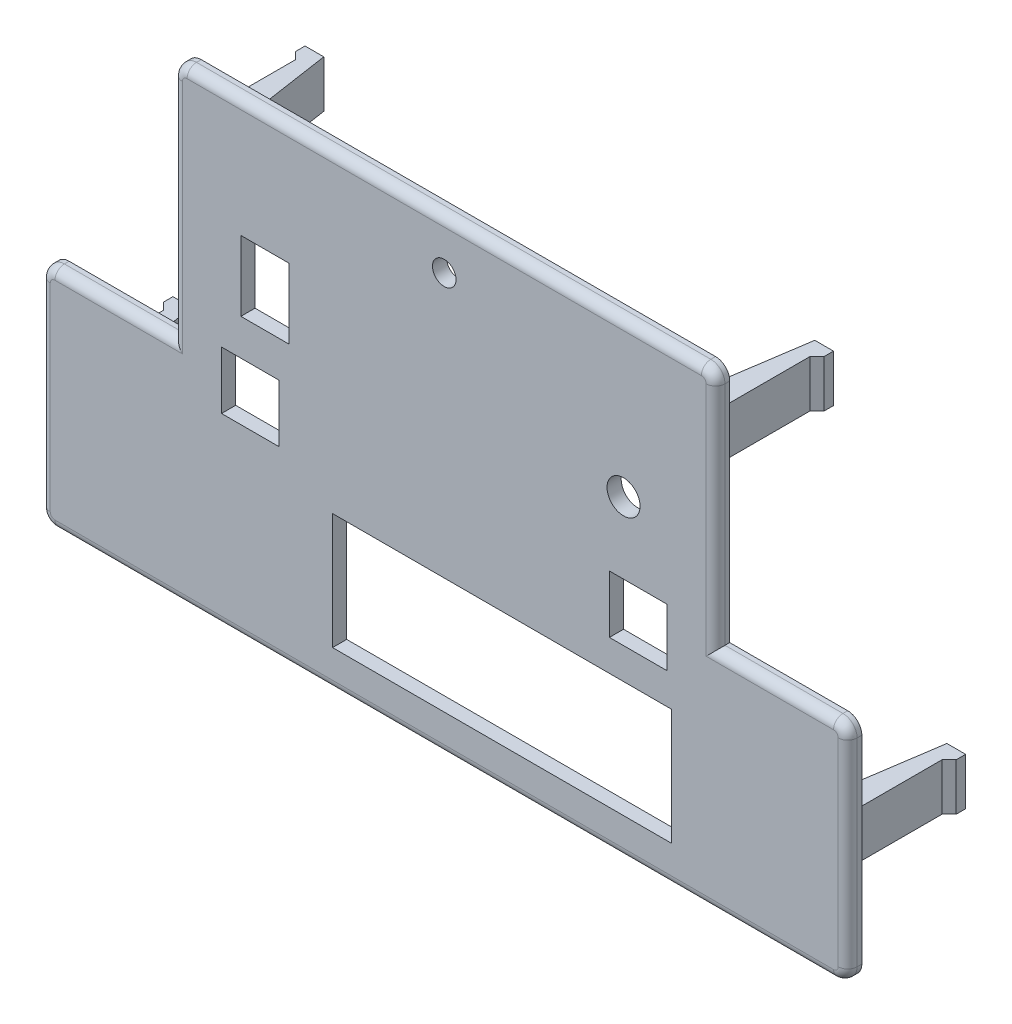
SolidWorks part; units mm, degrees
ref_plane "Front Plane" through (0, 0, 0) normal (0, 0, 1) x (1, 0, 0)
ref_plane "Top Plane" through (0, 0, 0) normal (0, 1, 0) x (1, 0, 0)
ref_plane "Right Plane" through (0, 0, 0) normal (1, 0, 0) x (0, 0, -1)
sketch "Sketch1" plane through (0, 0, 0) normal (0, 0, 1) x (1, 0, 0)
  line L0 (-115, -20.1143) -> (0, -20.1143) construction
  line L1 (0, 0) -> (-115, 0)
  line L2 (0, 0) -> (0, -51)
  line L3 (0, -99) -> (-115, -99)
  line L4 (-115, 0) -> (-115, -51)
  line L5 (28, -84.328) -> (-143, -84.328) construction
  line L6 (-115, -99) -> (-143, -99)
  line L7 (-143, -99) -> (-143, -51)
  line L8 (-115, -51) -> (-143, -51)
  line L9 (-57.5, -99) -> (-57.5, 0) construction
  line L10 (0, -99) -> (28, -99)
  line L11 (28, -99) -> (28, -51)
  line L12 (0, -51) -> (28, -51)
  line L13 (0, -96) -> (25, -96) construction
  line L14 (-9.3223, -91) -> (-81.1723, -91)
  line L15 (-9.3223, -91) -> (-9.3223, -66.4)
  line L16 (-9.3223, -66.4) -> (-81.1723, -66.4)
  line L17 (-81.1723, -91) -> (-81.1723, -66.4)
  line L18 (0, -51) -> (0, -99) construction
  line L19 (25, -96) -> (25, -54) construction
  line L20 (-3, -54) -> (25, -54) construction
  line L21 (-3, -3) -> (-3, -54) construction
  line L22 (-3, -3) -> (-112, -3) construction
  line L23 (-112, -3) -> (-112, -54) construction
  line L24 (-112, -54) -> (-140, -54) construction
  line L25 (-140, -96) -> (-140, -54) construction
  line L26 (-115, -96) -> (-140, -96) construction
  line L27 (0, -96) -> (-115, -96) construction
  line L34 (-100.6, -25.0685) -> (-90.4, -39.9185) construction
  line L35 (-104.7, -59.7974) -> (-92.5, -59.7974)
  line L36 (-104.7, -59.7974) -> (-104.7, -47.5974)
  line L37 (-104.7, -47.5974) -> (-92.5, -47.5974)
  line L38 (-92.5, -59.7974) -> (-92.5, -47.5974)
  line L39 (-100.6, -25.0685) -> (-90.4, -25.0685)
  line L40 (-100.6, -25.0685) -> (-100.6, -39.9185)
  line L41 (-100.6, -39.9185) -> (-90.4, -39.9185)
  line L42 (-90.4, -25.0685) -> (-90.4, -39.9185)
  line L43 (-92.5, -53.6974) -> (-22.5, -53.6974) construction
  line L44 (-10.3, -47.5974) -> (-22.5, -47.5974)
  line L45 (-10.3, -47.5974) -> (-10.3, -59.7974)
  line L46 (-10.3, -59.7974) -> (-22.5, -59.7974)
  line L47 (-22.5, -47.5974) -> (-22.5, -59.7974)
  line L48 (-95.5, -32.4935) -> (-57.5, -32.4935) construction
  line L49 (-57.5, -32.4935) -> (-19.5, -32.4935) construction
  circle A0 centre (-57.5, -10.3954) radius 2.5
  circle A1 centre (-19.5, -32.4935) radius 3.5
  point P35 (-57.5, -53.6974)
  dimension "D8" = 7
  dimension "D9" = 38
  dimension "3.6" = 5
  dimension "D1" = 115
  dimension "110" = 99
  dimension "D2" = 28
  dimension "D3" = 48
  dimension "D4" = 71.85
  dimension "D5" = 8
  dimension "22.3" = 24.6
  dimension "D7" = 10.2
  dimension "10" = 12.2
  dimension "13" = 14.85
  dimension "D10" = 70
  dimension "38" = 38
  dimension "D6" = 3
extrude "Boss-Extrude1" add sketch "Sketch1" along normal blind 3
sketch "Sketch2" plane through (0, 0, 3) normal (0, 0, 1) x (1, 0, 0)
  line L0 (-3, -54) -> (-3, -3)
  line L1 (-3, -3) -> (-112, -3)
  line L2 (-112, -3) -> (-112, -54)
  line L3 (-112, -54) -> (-140, -54)
  line L4 (-140, -54) -> (-140, -96)
  line L5 (-140, -96) -> (25, -96)
  line L6 (25, -96) -> (25, -54)
  line L7 (25, -54) -> (-3, -54)
  line L8 (0, -51) -> (0, 0)
  line L9 (0, 0) -> (-115, 0)
  line L10 (-115, 0) -> (-115, -51)
  line L11 (-115, -51) -> (-143, -51)
  line L12 (-143, -51) -> (-143, -99)
  line L13 (-143, -99) -> (28, -99)
  line L14 (28, -99) -> (28, -51)
  line L15 (28, -51) -> (0, -51)
  line L16 (0, -51) -> (0, 0)
  line L17 (0, 0) -> (-115, 0)
  line L18 (-115, 0) -> (-115, -51)
  line L19 (-115, -51) -> (-143, -51)
  line L20 (-143, -51) -> (-143, -99)
  line L21 (-143, -99) -> (28, -99)
  line L22 (28, -99) -> (28, -51)
  line L23 (28, -51) -> (0, -51)
  dimension "D1" = 0
  dimension "D2" = 3
fillet "Fillet1" radius 2 8 edges at (14, -51, 3) (0, -25.5, 3) (-57.5, 0, 3) (-129, -51, 3) (-115, -25.5, 3) (28, -75, 3) (-57.5, -99, 3) (-143, -75, 3)
fillet "Fillet2" radius 3 12 edges at (-142.4142, -51.5858, 2.4142) (-114.4142, -0.5858, 2.4142) (-0.5858, -0.5858, 2.4142) (27.4142, -51.5858, 2.4142) (27.4142, -98.4142, 2.4142) (-142.4142, -98.4142, 2.4142) (-143, -51, 0.5) (-115, 0, 0.5) (0, 0, 0.5) (28, -51, 0.5) (28, -99, 0.5) (-143, -99, 0.5)
ref_plane "Plane1" through (0, -60, 0) normal (0, 1, 0) x (1, 0, 0)
sketch "Sketch3" plane through (0, -60, 0) normal (0, 1, 0) x (1, 0, 0)
  line L0 (-57.5, -1) -> (-57.5, 35.742) construction
  line L1 (-112, -1) -> (-3, -1) construction
  line L2 (25, 0) -> (25, 20)
  line L3 (25, 20) -> (26.5, 21.5)
  line L4 (26.5, 21.5) -> (26.5, 23.5)
  line L5 (26.5, 23.5) -> (22.525, 23.5)
  line L6 (22.525, 23.5) -> (19, 0)
  line L7 (19, 0) -> (25, 0)
  line L8 (25, 0) -> (0, 0) construction
  line L9 (25, 20) -> (22, 20) construction
  line L10 (-3, 0) -> (-3, 20)
  line L11 (-3, 20) -> (-1.5, 21.5)
  line L12 (-1.5, 21.5) -> (-1.5, 23.5)
  line L13 (-1.5, 23.5) -> (-5.475, 23.5)
  line L14 (-5.475, 23.5) -> (-9, 0)
  line L15 (-9, 0) -> (-3, 0)
  line L16 (-3, 20) -> (-6, 20) construction
  line L17 (-112, 20) -> (-109, 20) construction
  line L18 (-140, 20) -> (-137, 20) construction
  line L19 (-106, 0) -> (-112, 0)
  line L20 (-109.525, 23.5) -> (-106, 0)
  line L21 (-113.5, 23.5) -> (-109.525, 23.5)
  line L22 (-113.5, 21.5) -> (-113.5, 23.5)
  line L23 (-112, 20) -> (-113.5, 21.5)
  line L24 (-112, 0) -> (-112, 20)
  line L25 (-134, 0) -> (-140, 0)
  line L26 (-137.525, 23.5) -> (-134, 0)
  line L27 (-141.5, 23.5) -> (-137.525, 23.5)
  line L28 (-141.5, 21.5) -> (-141.5, 23.5)
  line L29 (-140, 20) -> (-141.5, 21.5)
  line L30 (-140, 0) -> (-140, 20)
  dimension "D1" = 20
  dimension "D2" = 1.5
  dimension "D3" = 2
  dimension "D4" = 3
  dimension "D5" = 6
  dimension "D6" = 135
  dimension "D7" = 20
  dimension "D8" = 1.5
  dimension "D9" = 2
  dimension "D10" = 3
  dimension "D11" = 6
  dimension "D12" = 135
extrude "Boss-Extrude2" add sketch "Sketch3" against normal blind 10 from offset 10 contours L30 L29 L28 L27 L26 L25 | L2 L3 L4 L5 L6 L7 offset against normal yes
sketch "Sketch4" plane through (0, 0, 0) normal (0, 1, 0) x (1, 0, 0)
  line L18 (-112, 0) -> (-106, 0)
  line L19 (-112, 20) -> (-112, 0)
  line L20 (-113.5, 21.5) -> (-112, 20)
  line L21 (-113.5, 23.5) -> (-113.5, 21.5)
  line L22 (-109.525, 23.5) -> (-113.5, 23.5)
  line L23 (-106, 0) -> (-109.525, 23.5)
  line L24 (-112, 0) -> (-106, 0)
  line L25 (-112, 20) -> (-112, 0)
  line L26 (-113.5, 21.5) -> (-112, 20)
  line L27 (-113.5, 23.5) -> (-113.5, 21.5)
  line L28 (-109.525, 23.5) -> (-113.5, 23.5)
  line L29 (-106, 0) -> (-109.525, 23.5)
  line L30 (-1.5, 21.5) -> (-1.5, 23.5)
  line L31 (-1.5, 23.5) -> (-5.475, 23.5)
  line L32 (-5.475, 23.5) -> (-9, 0)
  line L33 (-9, 0) -> (-3, 0)
  line L34 (-3, 0) -> (-3, 20)
  line L35 (-3, 20) -> (-1.5, 21.5)
  line L36 (-1.5, 21.5) -> (-1.5, 23.5)
  line L37 (-1.5, 23.5) -> (-5.475, 23.5)
  line L38 (-5.475, 23.5) -> (-9, 0)
  line L39 (-9, 0) -> (-3, 0)
  line L40 (-3, 0) -> (-3, 20)
  line L41 (-3, 20) -> (-1.5, 21.5)
  dimension "D2" = 0
  dimension "D3" = 0
extrude "Boss-Extrude3" add sketch "Sketch4" against normal blind 10 from offset 10 offset against normal yes
